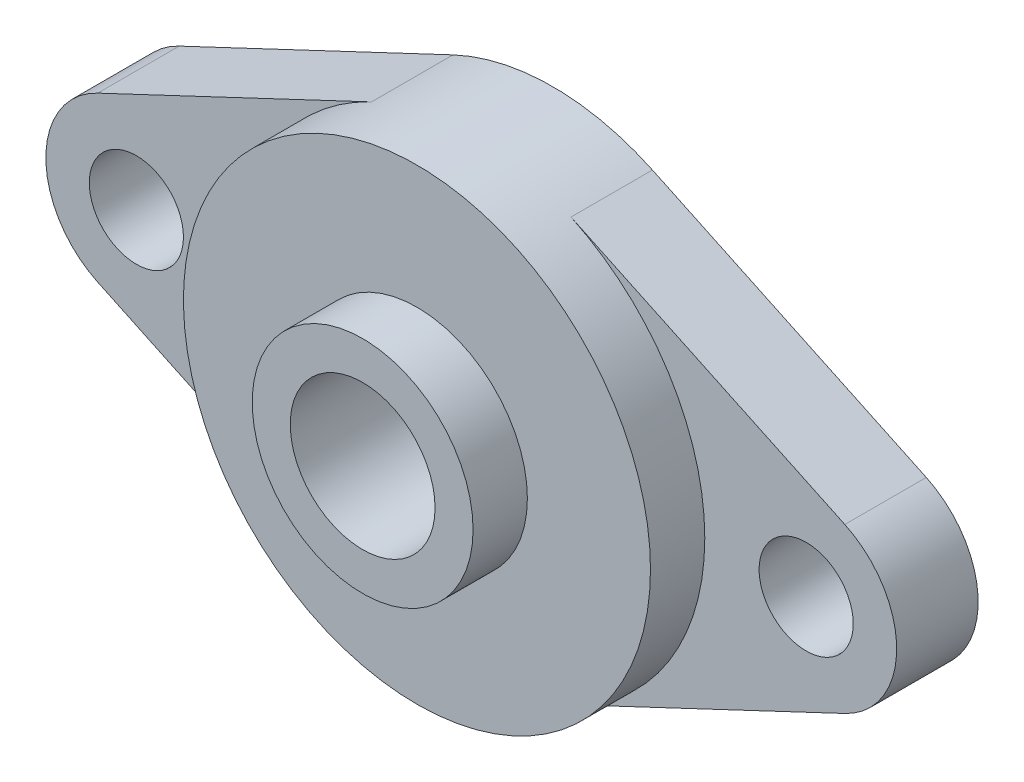
SolidWorks part; units mm, degrees
ref_plane "前视基准面" through (0, 0, 0) normal (0, 0, 1) x (1, 0, 0)
ref_plane "上视基准面" through (0, 0, 0) normal (0, 1, 0) x (1, 0, 0)
ref_plane "右视基准面" through (0, 0, 0) normal (1, 0, 0) x (0, 0, -1)
other "Configuration Table"
sketch "草图1" plane through (0, 0, 0) normal (0, 0, 1) x (1, 0, 0)
  line L0 (-18.5, 0) -> (18.5, 0) construction
  line L1 (-20.6351, 4.5212) -> (-5.5086, 11.6647)
  line L2 (5.5086, 11.6647) -> (20.6351, 4.5212)
  line L3 (20.6351, -4.5212) -> (5.5086, -11.6647)
  line L4 (-20.6351, -4.5212) -> (-5.5086, -11.6647)
  arc A0 (5.5086, 11.6647) -> (-5.5086, 11.6647) centre (0, 0) ccw
  circle A1 centre (18.5, 0) radius 2.6
  circle A2 centre (-18.5, 0) radius 2.6
  arc A3 (-20.6351, 4.5212) -> (-20.6351, -4.5212) centre (-18.5, 0) ccw
  arc A4 (20.6351, -4.5212) -> (20.6351, 4.5212) centre (18.5, 0) ccw
  arc A5 (-5.5086, -11.6647) -> (5.5086, -11.6647) centre (0, 0) ccw
  point P6 (0, 0)
  point P18 (0, 0)
  dimension "D1" = 25.8
  dimension "D3" = 5.2
  dimension "D4" = 5.2
  dimension "D5" = 10
  dimension "D6" = 10
  dimension "D2" = 37
extrude "凸台-拉伸1" add sketch "草图1" along normal blind 4.5
sketch "草图2" plane through (0, 0, 0) normal (0, 0, 1) x (1, 0, 0)
  circle A0 centre (0, 0) radius 12.9
  dimension "D1" = 25.8
extrude "凸台-拉伸2" add sketch "草图2" along normal blind 3 from surface starting at face at (21.1, 0, 4.5)
sketch "草图4" plane through (0, 0, 0) normal (0, 0, 1) x (1, 0, 0)
  circle A0 centre (0, 0) radius 6.1
  dimension "D1" = 12.2
extrude "凸台-拉伸3" add sketch "草图4" along normal blind 3 from surface starting at face at (12.9, 0, 7.5)
sketch "草图6" plane through (0, 0, 0) normal (0, 0, 1) x (1, 0, 0)
  circle A0 centre (0, 0) radius 4
  dimension "D1" = 8
extrude "切除-拉伸1" cut sketch "草图6" along normal up to surface (10.5 mm away) from surface up to face at (6.1, 0, 10.5) starting at face at (0, 0, 0)
